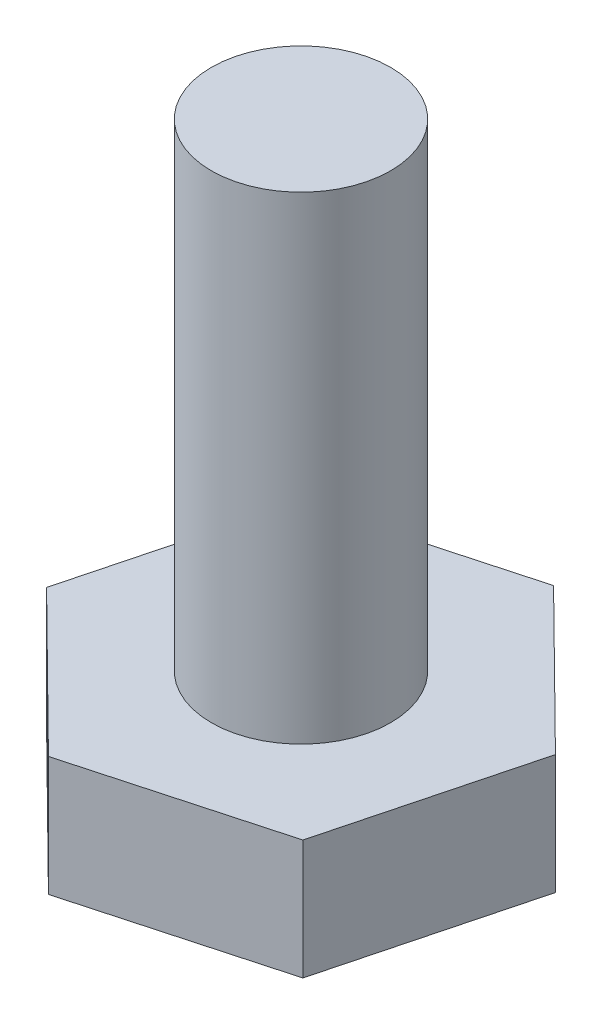
SolidWorks part; units mm, degrees
ref_plane "Front Plane" through (0, 0, 0) normal (0, 0, 1) x (1, 0, 0)
ref_plane "Top Plane" through (0, 0, 0) normal (0, 1, 0) x (1, 0, 0)
ref_plane "Right Plane" through (0, 0, 0) normal (1, 0, 0) x (0, 0, -1)
ref_axis "Axis1" through (0, -55, 0) along (0, 1, 0)
sketch "Sketch1" plane through (0, 0, 0) normal (0, 1, 0) x (1, 0, 0)
  line L1 (2.4652, -2.4337) -> (3.3402, 0.9181)
  line L2 (3.3402, 0.9181) -> (0.875, 3.3518)
  line L3 (0.875, 3.3518) -> (-2.4652, 2.4337)
  line L4 (-2.4652, 2.4337) -> (-3.3402, -0.9181)
  line L5 (-3.3402, -0.9181) -> (-0.875, -3.3518)
  line L6 (-0.875, -3.3518) -> (2.4652, -2.4337)
  circle A0 centre (0, 0) radius 3 construction
extrude "Boss-Extrude1" add sketch "Sketch1" along normal blind 2
sketch "Sketch2" plane through (0, 2, 0) normal (0, 1, 0) x (1, 0, 0)
  circle A0 centre (0, 0) radius 1.5
  dimension "D1" = 3
extrude "Boss-Extrude2" add sketch "Sketch2" along normal blind 8
equation "\"Length\"= 8"
equation "\"D1@Boss-Extrude2\"=\"Length\""
